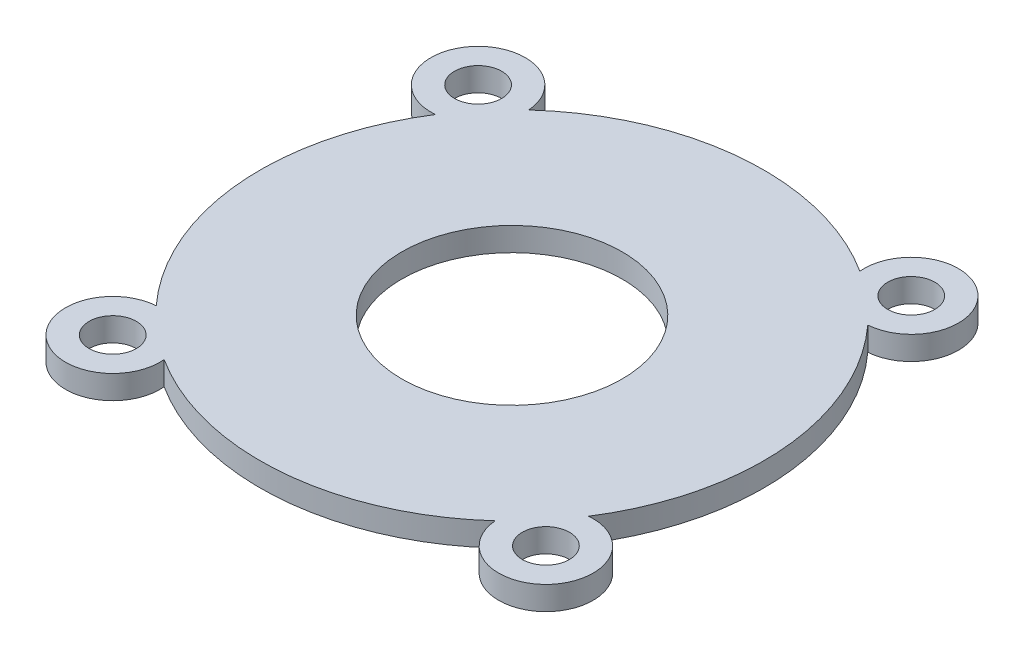
SolidWorks part; units mm, degrees
ref_plane "Front Plane" through (0, 0, 0) normal (0, 0, 1) x (1, 0, 0)
ref_plane "Top Plane" through (0, 0, 0) normal (0, 1, 0) x (1, 0, 0)
ref_plane "Right Plane" through (0, 0, 0) normal (1, 0, 0) x (0, 0, -1)
sketch "Sketch1" plane through (0, 0, 0) normal (0, 1, 0) x (1, 0, 0)
  circle B0 centre (0, 0) radius 7
  circle B1 centre (0, 0) radius 11
  circle B2 centre (0, 0) radius 13
  circle B3 centre (0, 0) radius 16
  circle B4 centre (11.6054, 13.7592) radius 1.5
  arc B5 (8.6184, 13.4805) -> (11.8343, 10.7679) centre (11.6054, 13.7592) cw
  arc B6 (13.4805, -8.6184) -> (10.7679, -11.8343) centre (13.7592, -11.6054) cw
  circle B7 centre (13.7592, -11.6054) radius 1.5
  arc B8 (-8.6184, -13.4805) -> (-11.8343, -10.7679) centre (-11.6054, -13.7592) cw
  circle B9 centre (-11.6054, -13.7592) radius 1.5
  arc B10 (-13.4805, 8.6184) -> (-10.7679, 11.8343) centre (-13.7592, 11.6054) cw
  circle B11 centre (-13.7592, 11.6054) radius 1.5
sketch_block_instance "Block1-1"
sketch_block "Block1" parameters "D2"=12, "D1"=18
extrude "Boss-Extrude1" add sketch "Sketch1" along normal blind 1.5 contours B2 B1 | B3 B2 | B1 B0 | B5 B3 B4 | B10 B3 B11 | B8 B3 B9 | B6 B3 B7 region at (-10.6889, 0, 0) region at (-12.6323, 0, 0) region at (14.9228, 0, 4.3626) region at (10.3706, 0, -12.2952) region at (15.9876, 0, 13.4849) region at (-12.2952, 0, -10.3706) region at (-13.4849, 0, 15.9876)
extrude "Boss-Extrude2" add sketch "Sketch1<3>" against normal blind 1 contours B2 B1 region at (-12.6323, 0, 0)
sketch "Sketch1<3>" plane through (0, 0, 0) normal (0, 1, 0) x (1, 0, 0) same geometry as "Sketch1"
